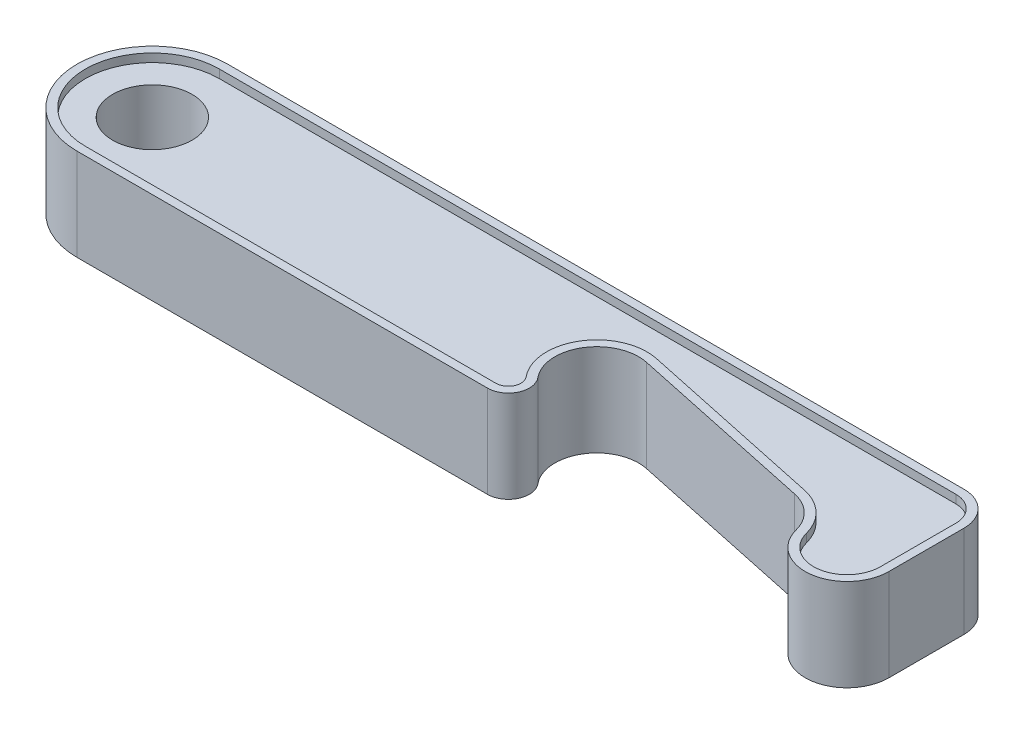
SolidWorks part; units mm, degrees
material "AISI 1020"
ref_plane "Front Plane" through (0, 0, 0) normal (0, 0, 1) x (1, 0, 0)
ref_plane "Top Plane" through (0, 0, 0) normal (0, 1, 0) x (1, 0, 0)
ref_plane "Right Plane" through (0, 0, 0) normal (1, 0, 0) x (0, 0, -1)
sketch "Sketch2" plane through (0, 0, 0) normal (0, 1, 0) x (1, 0, 0)
  line L0 (0, 9) -> (88, 9)
  line L1 (0, -9) -> (49.0402, -9)
  line L2 (92, 5) -> (92, -4)
  line L3 (78.3571, -1.6093) -> (55.8571, 3.1733)
  line L4 (0, 8) -> (88, 8)
  line L5 (91, 5) -> (91, -4)
  line L6 (78.565, -0.6311) -> (56.065, 4.1514)
  line L7 (0, -8) -> (49.0402, -8)
  circle A0 centre (0, 0) radius 4.75
  arc A1 (0, 9) -> (0, -9) centre (0, 0) ccw
  arc A2 (88, 9) -> (92, 5) centre (88, 5) cw
  arc A3 (92, -4) -> (82.1588, -5.25) centre (87, -4) cw
  arc A4 (82.1588, -5.25) -> (78.3571, -1.6093) centre (77.3175, -6.5) ccw
  arc A5 (55.8571, 3.1733) -> (50.966, -4.9058) centre (54.8175, -1.7175) ccw
  arc A6 (50.966, -4.9058) -> (49.0402, -9) centre (49.0402, -6.5) cw
  arc A7 (88, 8) -> (91, 5) centre (88, 5) cw
  arc A8 (91, -4) -> (83.127, -5) centre (87, -4) cw
  arc A9 (83.127, -5) -> (78.565, -0.6311) centre (77.3175, -6.5) ccw
  arc A10 (56.065, 4.1514) -> (50.1957, -5.5435) centre (54.8175, -1.7175) ccw
  arc A11 (50.1957, -5.5435) -> (49.0402, -8) centre (49.0402, -6.5) cw
  arc A12 (0, 8) -> (0, -8) centre (0, 0) ccw
  point P3 (77.1108, -5.4847)
  point P18 (82.3537, -5.8471)
  point P20 (78.594, -2.501)
  point P21 (49.8547, -6.4026)
  point P22 (78.7974, -3.0362)
  point P23 (82.3385, -5.8085)
  point P24 (0, 0)
  point P41 (0, 0)
  point P42 (0, 0)
  point P43 (0, 0)
  dimension "D1" = 9.5
  dimension "D4" = 4
  dimension "D5" = 5
  dimension "D6" = 5
  dimension "D7" = 5
  dimension "D8" = 2.5
  dimension "D2" = 18
  dimension "D3" = 101
  dimension "D9" = 22.5
  dimension "D10" = 12
  dimension "D11" = 1
extrude "Boss-Extrude1" add sketch "Sketch2" along normal mid plane 9 contours L4 A12 L7 A11 A10 L6 A9 A8 L5 A7 A0 region at (38.4301, 0, -0.8544)
extrude "Boss-Extrude2" add sketch "Sketch2<3>" along normal mid plane 11 contours A6 A5 L3 A4 A3 L2 A2 L0 A1 L1 A12 L4 A7 L5 A8 A9 L6 A10 A11 L7 region at (44, 0, -8.8974)
sketch "Sketch2<3>" plane through (0, 0, 0) normal (0, 1, 0) x (1, 0, 0) same geometry as "Sketch2"
equation "\"A\" = 101"
equation "\"B\" = 11"
equation "\"C\"= 1"
equation "\"D3@Sketch2\"=\"A\""
equation "\"D11@Sketch2\"=\"C\""
equation "\"D1@Boss-Extrude1\"=\"B\"-\"C\"-\"C\""
equation "\"D1@Boss-Extrude2\"=\"B\""
